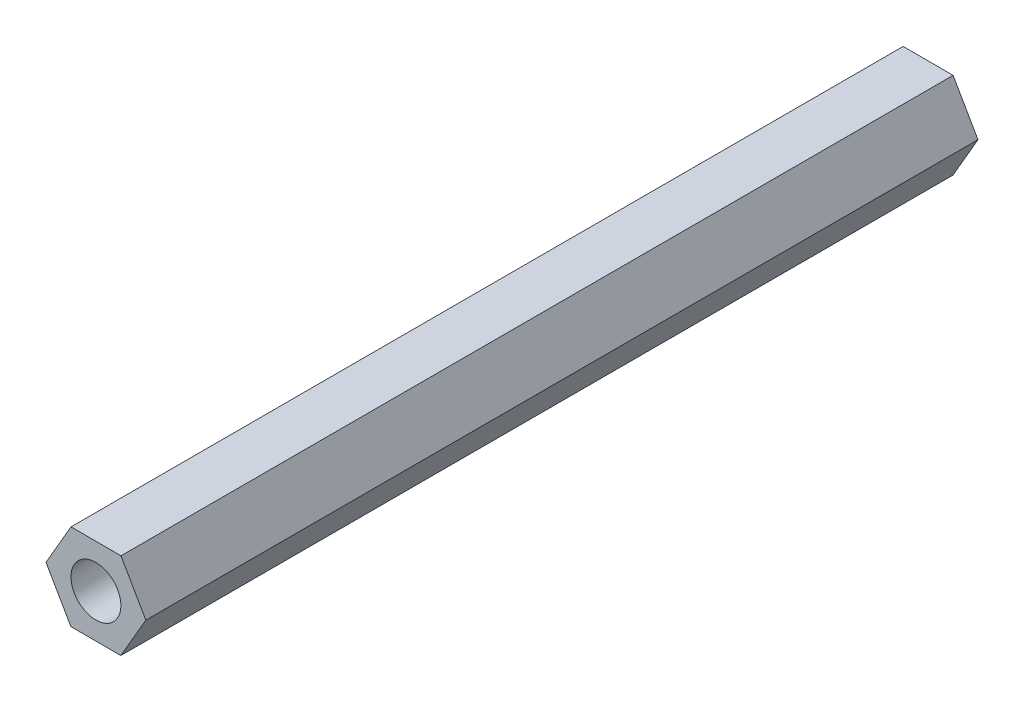
SolidWorks part; units mm, degrees
ref_plane "前视基准面" through (0, 0, 0) normal (0, 0, 1) x (1, 0, 0)
ref_plane "上视基准面" through (0, 0, 0) normal (0, 1, 0) x (1, 0, 0)
ref_plane "右视基准面" through (0, 0, 0) normal (1, 0, 0) x (0, 0, -1)
ref_plane "基准面1" through (0, 0, 0) normal (0, -1, 0) x (1, 0, 0)
sketch "草图1" plane through (0, 0, 0) normal (0, -1, 0) x (1, 0, 0)
  line L0 (2.5, 50) -> (1.5, 50)
  line L1 (1.5, 50) -> (1.5, 0)
  line L2 (1.5, 0) -> (2.5, 0)
  line L3 (2.5, 0) -> (2.5, 50)
  line L4 (0, 50) -> (0, 0) construction
revolve "旋转1" add sketch "草图1" angle 360 about L4 reverse direction yes
sketch "草图5" plane through (0, 0, 0) normal (0, 0, -1) x (-1, 0, 0)
  line L1 (-1.5042, 2.5956) -> (-3, -0.0049)
  line L2 (-3, -0.0049) -> (-1.4958, -2.6005)
  line L3 (-1.4958, -2.6005) -> (1.5042, -2.5956)
  line L4 (1.5042, -2.5956) -> (3, 0.0049)
  line L5 (3, 0.0049) -> (1.4958, 2.6005)
  line L6 (1.4958, 2.6005) -> (-1.5042, 2.5956)
  circle A0 centre (0, 0) radius 2.5981 construction
  circle A1 centre (0, 0) radius 1.5
  dimension "D1" = 3
  dimension "D2" = 3
extrude "凸台-拉伸4" add sketch "草图5" against normal blind 50
